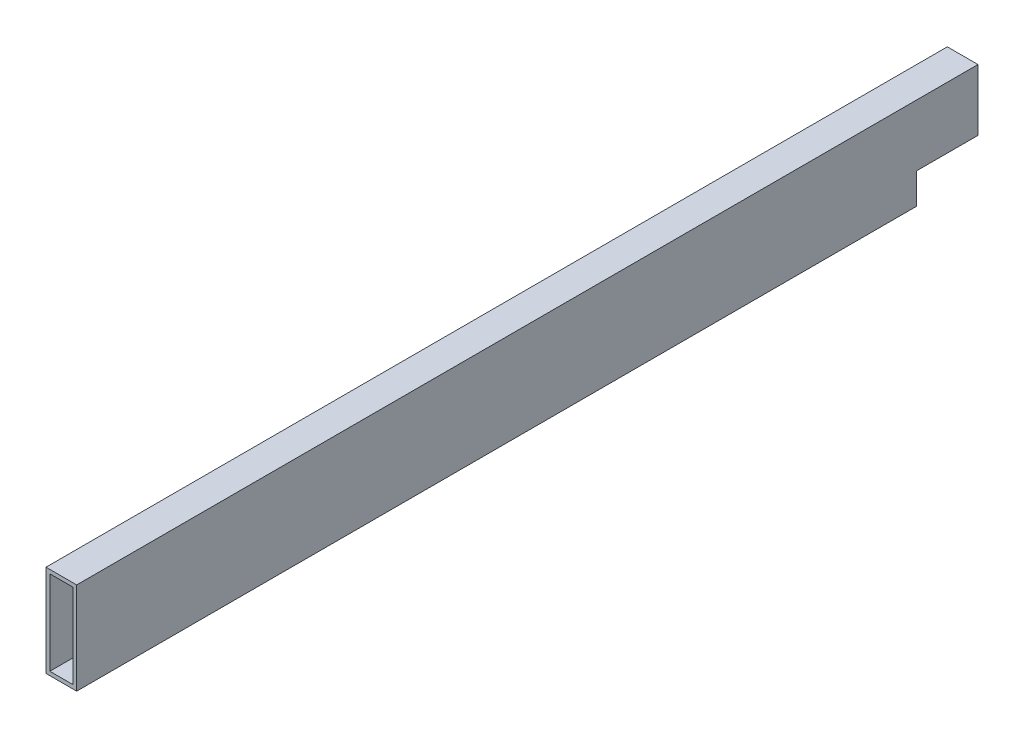
SolidWorks part; units mm, degrees
ref_plane "Front Plane" through (0, 0, 0) normal (0, 0, 1) x (1, 0, 0)
ref_plane "Top Plane" through (0, 0, 0) normal (0, 1, 0) x (1, 0, 0)
ref_plane "Right Plane" through (0, 0, 0) normal (1, 0, 0) x (0, 0, -1)
sketch "Sketch1" plane through (0, 0, 0) normal (0, 0, 1) x (1, 0, 0)
  line L1 (-12.7, -38.1) -> (12.7, -38.1)
  line L2 (-12.7, -38.1) -> (-12.7, 38.1)
  line L3 (-12.7, 38.1) -> (12.7, 38.1)
  line L4 (12.7, -38.1) -> (12.7, 38.1)
  line L5 (-12.7, -38.1) -> (12.7, 38.1) construction
  line L6 (-12.7, 38.1) -> (12.7, -38.1) construction
  point P0 (0, 0)
  dimension "D1" = 25.4
  dimension "D2" = 76.2
extrude "Boss-Extrude1" add sketch "Sketch1" along normal mid plane 745.998
shell "Shell1" thickness 3.175 removed face at (0, 0, -372.999) removed face at (0, 0, 372.999)
sketch "Sketch2" plane through (12.7, 0, 0) normal (1, 0, 0) x (0, 0, -1)
  line L1 (372.999, -38.1) -> (322.199, -38.1)
  line L2 (372.999, -38.1) -> (372.999, -12.7)
  line L3 (372.999, -12.7) -> (322.199, -12.7)
  line L4 (322.199, -38.1) -> (322.199, -12.7)
  dimension "D1" = 25.4
  dimension "D2" = 50.8
extrude "Cut-Extrude1" cut sketch "Sketch2" against normal through all
